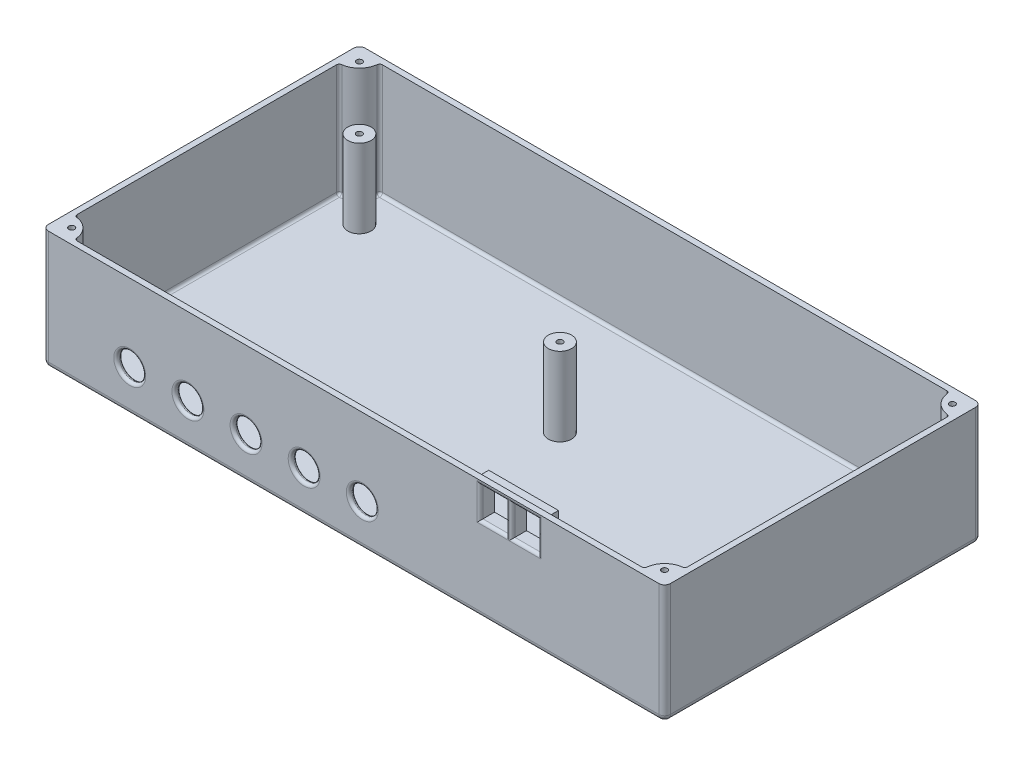
SolidWorks part; units mm, degrees
ref_plane "Front Plane" through (0, 0, 0) normal (0, 0, 1) x (1, 0, 0)
ref_plane "Top Plane" through (0, 0, 0) normal (0, 1, 0) x (1, 0, 0)
ref_plane "Right Plane" through (0, 0, 0) normal (1, 0, 0) x (0, 0, -1)
sketch "Sketch2" plane through (0, 0, 0) normal (0, 1, 0) x (1, 0, 0)
  line L1 (107, 54.5) -> (-107, 54.5)
  line L2 (107, 54.5) -> (107, -54.5)
  line L3 (107, -54.5) -> (-107, -54.5)
  line L4 (-107, 54.5) -> (-107, -54.5)
  line L5 (107, 54.5) -> (-107, -54.5) construction
  line L6 (107, -54.5) -> (-107, 54.5) construction
  point P0 (0, 0)
  dimension "D1" = 214
  dimension "D2" = 109
extrude "Boss-Extrude1" add sketch "Sketch2" along normal blind 41
sketch "Sketch3" plane through (0, 41, 0) normal (0, 1, 0) x (1, 0, 0)
  line L1 (98, 52.5) -> (-98, 52.5)
  line L2 (105, 45.5) -> (105, -45.5)
  line L3 (98, -52.5) -> (-98, -52.5)
  line L4 (-105, 45.5) -> (-105, -45.5)
  line L5 (105, 52.5) -> (-105, -52.5) construction
  line L6 (105, -52.5) -> (-105, 52.5) construction
  line L8 (107, 54.5) -> (-107, 54.5) construction
  line L9 (107, -54.5) -> (107, 54.5) construction
  line L10 (-107, 54.5) -> (-107, -54.5) construction
  line L11 (-107, -54.5) -> (107, -54.5) construction
  arc A0 (-105, 45.5) -> (-98, 52.5) centre (-105, 52.5) ccw
  arc A1 (98, 52.5) -> (105, 45.5) centre (105, 52.5) ccw
  arc A2 (105, -45.5) -> (98, -52.5) centre (105, -52.5) ccw
  arc A3 (-98, -52.5) -> (-105, -45.5) centre (-105, -52.5) ccw
  point P0 (0, 0)
  dimension "D1" = 2
  dimension "D7" = 7
  dimension "D10" = 7
  dimension "D12" = 7
  dimension "D14" = 7
  dimension "D2" = 2
  dimension "D3" = 2
  dimension "D4" = 2
  dimension "D5" = 2
  dimension "D6" = 2
  dimension "D8" = 2
  dimension "D9" = 2
  dimension "D11" = 2
  dimension "D13" = 2
extrude "Cut-Extrude1" cut sketch "Sketch3" against normal blind 39
sketch "Sketch4" plane through (0, 0, 54.5) normal (0, 0, 1) x (1, 0, 0)
  line L0 (-107, 41) -> (-107, 0) construction
  line L1 (-107, 0) -> (107, 0) construction
  circle A0 centre (-77, 14.5) radius 4.5
  circle A1 centre (-57, 14.5) radius 4.5
  circle A2 centre (-37, 14.5) radius 4.5
  circle A3 centre (-17, 14.5) radius 4.5
  circle A4 centre (3, 14.5) radius 4.5
  dimension "D3" = 9
  dimension "D9" = 20
  dimension "D1" = 30
  dimension "D2" = 14.5
  dimension "D4" = 5
extrude "Cut-Extrude2" cut sketch "Sketch4" against normal blind 3
sketch "Sketch5" plane through (0, 2, 0) normal (0, 1, 0) x (1, 0, 0)
  line L0 (-107, 54.5) -> (-107, -54.5) construction
  line L1 (107, 54.5) -> (-107, 54.5) construction
  circle A0 centre (-92.5, 40) radius 4
  circle A1 centre (4, 12.5) radius 4
  dimension "D1" = 8
  dimension "D2" = 8
  dimension "D3" = 14.5
  dimension "D4" = 14.5
  dimension "D5" = 42
  dimension "D6" = 111
extrude "Boss-Extrude2" add sketch "Sketch5" along normal blind 27
sketch "Sketch7" plane through (0, 0, 54.5) normal (0, 0, 1) x (1, 0, 0)
  line L0 (-107, 41) -> (-107, 0) construction
  line L1 (41.5, 40.5) -> (65.5, 40.5)
  line L2 (41.5, 40.5) -> (41.5, 27)
  line L3 (41.5, 27) -> (65.5, 27)
  line L4 (65.5, 40.5) -> (65.5, 27)
  line L5 (-107, 41) -> (107, 41) construction
  line L6 (-107, 0) -> (107, 0) construction
  dimension "D1" = 148.5
  dimension "D2" = 24
  dimension "D3" = 0.5
  dimension "D4" = 27
extrude "Boss-Extrude5" add sketch "Sketch7" against normal blind 5
sketch "Sketch8" plane through (0, 0, 54.5) normal (0, 0, 1) x (1, 0, 0)
  line L0 (-107, 41) -> (-107, 0) construction
  line L1 (43.5, 39.5) -> (52.5, 39.5)
  line L2 (43.5, 39.5) -> (43.5, 29)
  line L3 (43.5, 29) -> (52.5, 29)
  line L4 (52.5, 39.5) -> (52.5, 29)
  line L5 (54.5, 39.5) -> (63.5, 39.5)
  line L6 (54.5, 39.5) -> (54.5, 29)
  line L7 (54.5, 29) -> (63.5, 29)
  line L8 (63.5, 39.5) -> (63.5, 29)
  line L10 (-107, 0) -> (107, 0) construction
  line L11 (-107, 41) -> (107, 41) construction
  dimension "D1" = 150.5
  dimension "D2" = 9
  dimension "D3" = 2
  dimension "D4" = 9
  dimension "D5" = 1.5
  dimension "D7" = 29
extrude "Cut-Extrude3" cut sketch "Sketch8" against normal blind 5
fillet "Fillet1" radius 2 8 edges at (-107, 0, 0) (0, 0, 54.5) (107, 0, 0) (0, 0, -54.5) (-107, 20.5, -54.5) (107, 20.5, -54.5) (107, 20.5, 54.5) (-107, 20.5, 54.5)
fillet "Fillet2" radius 1 8 edges at (59, 39.5, 54.5) (54.5, 34.25, 54.5) (59, 29, 54.5) (63.5, 34.25, 54.5) (48, 29, 54.5) (52.5, 34.25, 54.5) (48, 39.5, 54.5) (43.5, 34.25, 54.5)
hole_wizard "Ø2.0mm Dowel Hole1" positions "3DSketch2" profile "Sketch12" hole size "Ø2.0" standard "ANSI Metric"
sketch3d "3DSketch2"
  line L0 (-105, 41, 54.5) -> (105, 41, 54.5) construction
  line L1 (-107, 41, -52.5) -> (-107, 41, 52.5) construction
  line L2 (105, 41, -54.5) -> (-105, 41, -54.5) construction
  line L3 (107, 41, 52.5) -> (107, 41, -52.5) construction
  line L4 (-92.5, 29, -40) -> (-92.5, 2, -40) construction
  line L5 (4, 29, -12.5) -> (4, 2, -12.5) construction
  point P0 (-102, 41, 49.5)
  point P2 (102, 41, -49.5)
  point P4 (102, 41, 49.5)
  point P6 (-102, 41, 49.5)
  point P18 (-102, 41, -49.5)
  point P19 (-92.5, 29, -40)
  point P23 (4, 29, -12.5)
  dimension "D1" = 5
  dimension "D2" = 5
  dimension "D3" = 5
  dimension "D4" = 5
  dimension "D5" = 5
  dimension "D6" = 5
  dimension "D7" = 5
  dimension "D8" = 5
sketch "Sketch12" plane through (-102, 41, 49.5) normal (1, 0, 0) x (0, 0, 1)
  line L0 (0, 0) -> (0, 20.6009)
  line L1 (0, 20.6009) -> (1, 20)
  line L2 (1, 20) -> (1, 0)
  line L5 (1, 0) -> (0, 0)
  line L10 (0, 20.6009) -> (-1, 20) construction
  line L11 (0, -6.35) -> (0, 107.95) construction
  dimension "Hole Dia." = 2
  dimension "Hole Depth" = 20
  dimension "Drill Angle" = 118
fillet "Fillet4" radius 1 10 edges at (-72.5, 14.5, 52.5) (-72.5, 14.5, 54.5) (-52.5, 14.5, 52.5) (-52.5, 14.5, 54.5) (7.5, 14.5, 52.5) (7.5, 14.5, 54.5) (-12.5, 14.5, 52.5) (-12.5, 14.5, 54.5) (-32.5, 14.5, 52.5) (-32.5, 14.5, 54.5)
fillet "Fillet5" radius 1 16 edges at (105, 2, 0) (100.0503, 2, 47.5503) (0, 2, 52.5) (-100.0503, 2, 47.5503) (-105, 2, 0) (-100.0503, 2, -47.5503) (0, 2, -52.5) (100.0503, 2, -47.5503) (-98, 21.5, 52.5) (-105, 21.5, 45.5) (98, 21.5, 52.5) (105, 21.5, 45.5) (105, 21.5, -45.5) (98, 21.5, -52.5) (-98, 21.5, -52.5) (-105, 21.5, -45.5)
